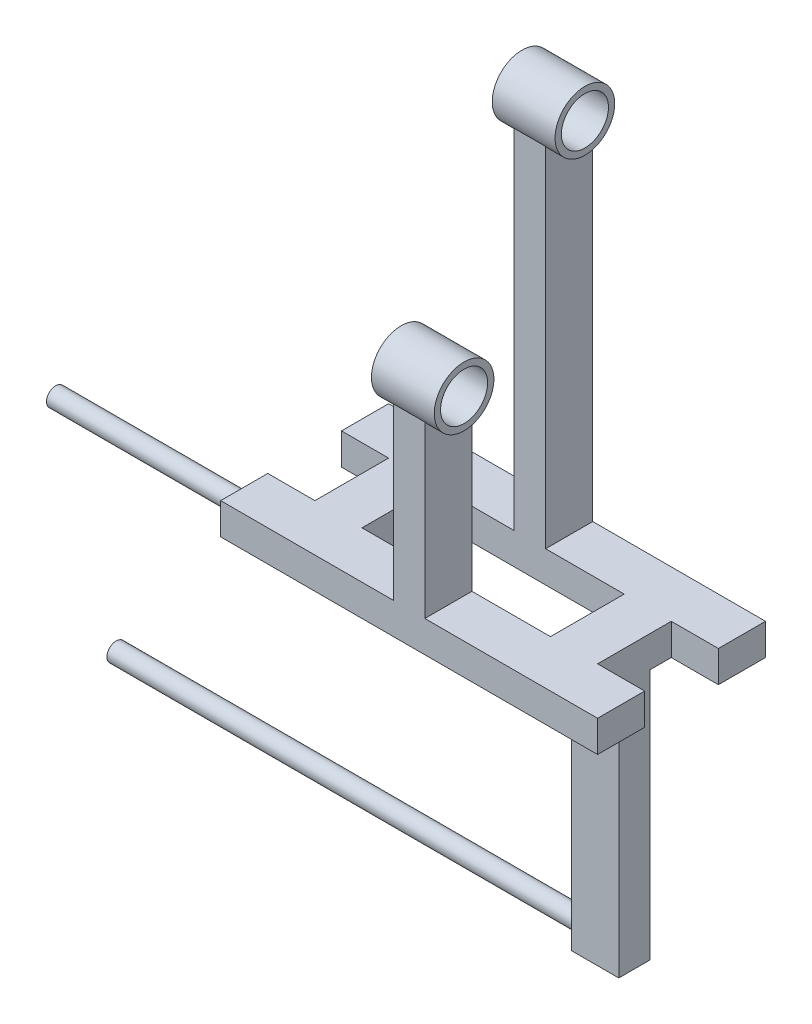
SolidWorks part; units mm, degrees
ref_plane "Front Plane" through (0, 0, 0) normal (0, 0, 1) x (1, 0, 0)
ref_plane "Top Plane" through (0, 0, 0) normal (0, 1, 0) x (1, 0, 0)
ref_plane "Right Plane" through (0, 0, 0) normal (1, 0, 0) x (0, 0, -1)
sketch "Sketch2" plane through (0, 0, 0) normal (0, 1, 0) x (1, 0, 0)
  line L33 (60, -15) -> (-60, -15)
  line L34 (-60, -15) -> (-60, 0)
  line L46 (-60, 0) -> (-45, 0)
  line L47 (-45, 0) -> (-45, 23.4666)
  line L48 (-45, 23.4666) -> (-60, 23.4666)
  line L49 (-60, 23.4666) -> (-60, 38.4666)
  line L50 (-60, 38.4666) -> (60, 38.4666)
  line L51 (60, 38.4666) -> (60, 23.4666)
  line L52 (60, 23.4666) -> (45, 23.4666)
  line L53 (45, 23.4666) -> (45, 0)
  line L54 (45, 0) -> (60, 0)
  line L55 (60, 0) -> (60, -15)
  line L57 (-30, 0) -> (30, 0)
  line L58 (-30, 0) -> (-30, 23.4666)
  line L59 (-30, 23.4666) -> (30, 23.4666)
  line L60 (30, 0) -> (30, 23.4666)
  point P21 (0, 0)
  dimension "D1" = 120
  dimension "D2" = 53.4666
  dimension "D3" = 15
  dimension "D4" = 60
  dimension "D5" = 15
  dimension "D6" = 15
extrude "Boss-Extrude2" add sketch "Sketch2" along normal blind 10
sketch "Sketch3" plane through (0, 10, 0) normal (0, 1, 0) x (1, 0, 0)
  line L0 (-30, 0) -> (30, 0) construction
  line L1 (-5, 0) -> (5, 0)
  line L2 (-5, 0) -> (-5, -15)
  line L3 (-5, -15) -> (5, -15)
  line L4 (5, 0) -> (5, -15)
  line L5 (-60, -15) -> (60, -15) construction
  line L6 (60, 38.4666) -> (-60, 38.4666) construction
  line L7 (-5, 38.4666) -> (5, 38.4666)
  line L8 (-5, 38.4666) -> (-5, 23.4666)
  line L9 (-5, 23.4666) -> (5, 23.4666)
  line L10 (5, 38.4666) -> (5, 23.4666)
  line L11 (30, 23.4666) -> (-30, 23.4666) construction
  dimension "D1" = 5
  dimension "D2" = 10
extrude "Boss-Extrude3" add sketch "Sketch3" along normal blind 60
sketch "Sketch4" plane through (0, 70, 0) normal (0, 1, 0) x (1, 0, 0)
  line L4 (-5, 38.4666) -> (-5, 23.4666)
  line L5 (-5, 23.4666) -> (5, 23.4666)
  line L6 (5, 23.4666) -> (5, 38.4666)
  line L7 (5, 38.4666) -> (-5, 38.4666)
  line L8 (-5, 38.4666) -> (-5, 23.4666)
  line L9 (-5, 23.4666) -> (5, 23.4666)
  line L10 (5, 23.4666) -> (5, 38.4666)
  line L11 (5, 38.4666) -> (-5, 38.4666)
  dimension "D1" = 0
extrude "Boss-Extrude4" add sketch "Sketch4" along normal blind 56.7503
sketch "Sketch6" plane through (0, 0, 0) normal (1, 0, 0) x (0, 0, -1)
  line L0 (-15, 70) -> (0, 70) construction
  line L1 (23.4666, 126.7503) -> (38.4666, 126.7503) construction
  line L2 (0, 70) -> (0, 10) construction
  line L3 (38.4666, 126.7503) -> (38.4666, 10) construction
  circle A0 centre (-7.5, 70) radius 7.5
  circle A1 centre (30.9666, 126.7503) radius 7.5
  dimension "D1" = 15
  dimension "D2" = 7.5
  dimension "D3" = 7.5
extrude "Extrude-Thin1" add sketch "Sketch6" along normal mid plane 20 thin thin type one direction wall 2
sketch "Sketch7" plane through (5, 0, 0) normal (1, 0, 0) x (0, 0, -1)
  line L1 (0, 70) -> (-15, 70)
  line L2 (0, 70) -> (-15, 70)
  line L3 (38.4666, 126.7503) -> (23.4666, 126.7503)
  line L4 (38.4666, 126.7503) -> (23.4666, 126.7503)
  arc A1 (-15, 70) -> (0, 70) centre (-7.5, 70) ccw
  arc A2 (-15, 70) -> (0, 70) centre (-7.5, 70) ccw
  arc A3 (23.4666, 126.7503) -> (38.4666, 126.7503) centre (30.9666, 126.7503) ccw
  arc A4 (23.4666, 126.7503) -> (38.4666, 126.7503) centre (30.9666, 126.7503) ccw
  dimension "D1" = 0
  dimension "D2" = 0
extrude "Cut-Extrude1" cut sketch "Sketch7" against normal through all both and the other way through all
sketch "Sketch8" plane through (0, 0, 0) normal (0, -1, 0) x (1, 0, 0)
  line L0 (30, 0) -> (30, -23.4666) construction
  line L1 (30, -16.75) -> (45, -16.75)
  line L2 (30, -16.75) -> (30, -6.75)
  line L3 (30, -6.75) -> (45, -6.75)
  line L4 (45, -16.75) -> (45, -6.75)
  line L5 (45, 0) -> (45, -23.4666) construction
  line L6 (-60, 15) -> (60, 15) construction
  dimension "D1" = 10
  dimension "D2" = 21.75
extrude "Boss-Extrude5" add sketch "Sketch8" along normal blind 80
sketch "Sketch9" plane through (30, 0, 0) normal (-1, 0, 0) x (0, 0, 1)
  line L0 (-6.75, -80) -> (-6.75, 0) construction
  line L1 (-6.75, -80) -> (-16.75, -80) construction
  circle A0 centre (-11.75, -75) radius 2.95
  dimension "D1" = 5.9
  dimension "D2" = 5
  dimension "D3" = 5
extrude "Boss-Extrude6" add sketch "Sketch9" along normal blind 150
sketch "Sketch10" plane through (-60, 0, 0) normal (-1, 0, 0) x (0, 0, 1)
  line L0 (0, 10) -> (15, 10) construction
  line L1 (15, 10) -> (15, 0) construction
  circle A0 centre (7.5, 5) radius 2.95
  dimension "D1" = 5.9
  dimension "D2" = 5
  dimension "D3" = 7.5
extrude "Boss-Extrude7" add sketch "Sketch10" along normal blind 60
